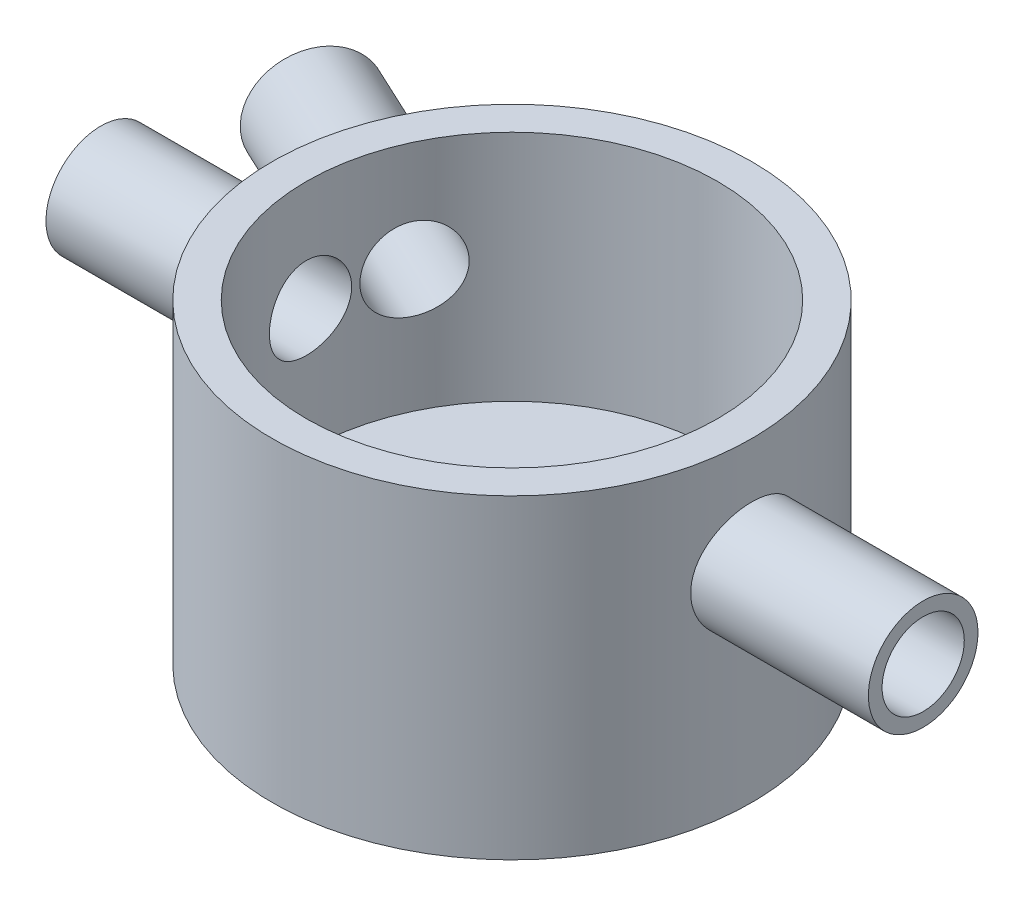
SolidWorks part; units mm, degrees
ref_plane "Plano frontal" through (0, 0, 0) normal (0, 0, 1) x (1, 0, 0)
ref_plane "Plano superior" through (0, 0, 0) normal (0, 1, 0) x (1, 0, 0)
ref_plane "Plano direito" through (0, 0, 0) normal (1, 0, 0) x (0, 0, -1)
sketch "Esboço1" plane through (0, 0, 0) normal (0, 0, 1) x (1, 0, 0)
  line L0 (0, 0) -> (0, 24.7405) construction
  line L1 (0, 0) -> (30.393, 0) construction
  line L2 (0, -15) -> (17.5, -15)
  line L3 (17.5, -15) -> (17.5, 8)
  line L4 (17.5, 8) -> (15, 8)
  line L5 (15, 8) -> (15, -9)
  line L6 (15, -9) -> (5, -9)
  line L7 (5, -9) -> (5, -11.5)
  line L8 (5, -11.5) -> (3.25, -11.5)
  line L9 (0, -12.5) -> (0, -15)
  line L10 (3.25, -11.5) -> (3.25, -12.5)
  line L11 (3.25, -12.5) -> (0, -12.5)
  point P9 (15, -0.5)
  dimension "D1" = 35
  dimension "D2" = 30
  dimension "D3" = 2.5
  dimension "D4" = 23
  dimension "D5" = 8
  dimension "D6" = 3.5
  dimension "D7" = 6.5
  dimension "D8" = 10
  dimension "D9" = 9
revolve "Revolução1" add sketch "Esboço1" angle 360 about L0
hole_wizard "Furos-guia com Ø6.0mm1" positions "3DSketch1" profile "Esboço2" hole size "Ø6.0" standard "Ansi Metric" end condition through all
sketch3d "3DSketch1"
  point P0 (-17.5, 0, 0)
sketch "Esboço2" plane through (-17.5, 0, 0) normal (0, 1, 0) x (0, 0, 1)
  line L0 (0, 0) -> (0, 35)
  line L1 (0, 35) -> (3, 35)
  line L2 (3, 35) -> (3, 0)
  line L5 (3, 0) -> (0, 0)
  line L11 (0, -6.35) -> (0, 107.95) construction
  dimension "Thru Hole Dia." = 6
  dimension "Thru Hole Depth" = 35
hole_wizard "Furos-guia com Ø6.0mm2" positions "3DSketch2" profile "Esboço3" hole size "Ø6.0" standard "Ansi Metric" end condition up to next
sketch3d "3DSketch2"
  line L0 (0, 0, 0) -> (-15.8604, 0, -7.3958) construction
  line L3 (0, 0, 0) -> (-17.5, 0, 0) construction
  point P0 (-15.8604, 0, -7.3958)
  dimension "D1" = 25
sketch "Esboço3" plane through (-15.8604, 0, -7.3958) normal (0, 1, 0) x (-0.4226, 0, 0.9063)
  line L0 (0, 0) -> (0, 2.5)
  line L1 (0, 2.5) -> (3, 2.5)
  line L2 (3, 2.5) -> (3, 0)
  line L5 (3, 0) -> (0, 0)
  line L11 (0, -6.35) -> (0, 107.95) construction
  dimension "Thru Hole Dia." = 6
  dimension "Thru Hole Depth" = 2.5
sketch "Esboço4" plane through (0, 0, 0) normal (1, 0, 0) x (0, 0, -1)
  circle A0 centre (0, 0) radius 3
  circle A1 centre (0, 0) radius 4
  circle A2 centre (0, 0) radius 3 construction
  dimension "D1" = 1
extrude "Ressalto-extrusão1" add sketch "Esboço4" along normal up to next from offset 30 offset against normal yes
mirror "Espelhar3" about plane through (0, 0, 0) normal (1, 0, 0) of "Ressalto-extrusão1"
ref_axis "Eixo1" through (0, 8, 0) along (0, -1, 0)
ref_plane "Plano1" through (0, 0, 0) normal (0.9063, 0, 0.4226) x (0, -1, 0)
sketch "Esboço5" plane through (0, 0, 0) normal (0.9063, 0, 0.4226) x (0, -1, 0)
  circle A0 centre (0, 0) radius 4
  circle A1 centre (0, 0) radius 3 construction
  circle A2 centre (0, 0) radius 3
  dimension "D1" = 1
extrude "Ressalto-extrusão2" add sketch "Esboço5" along normal up to next from offset 30 offset against normal yes
